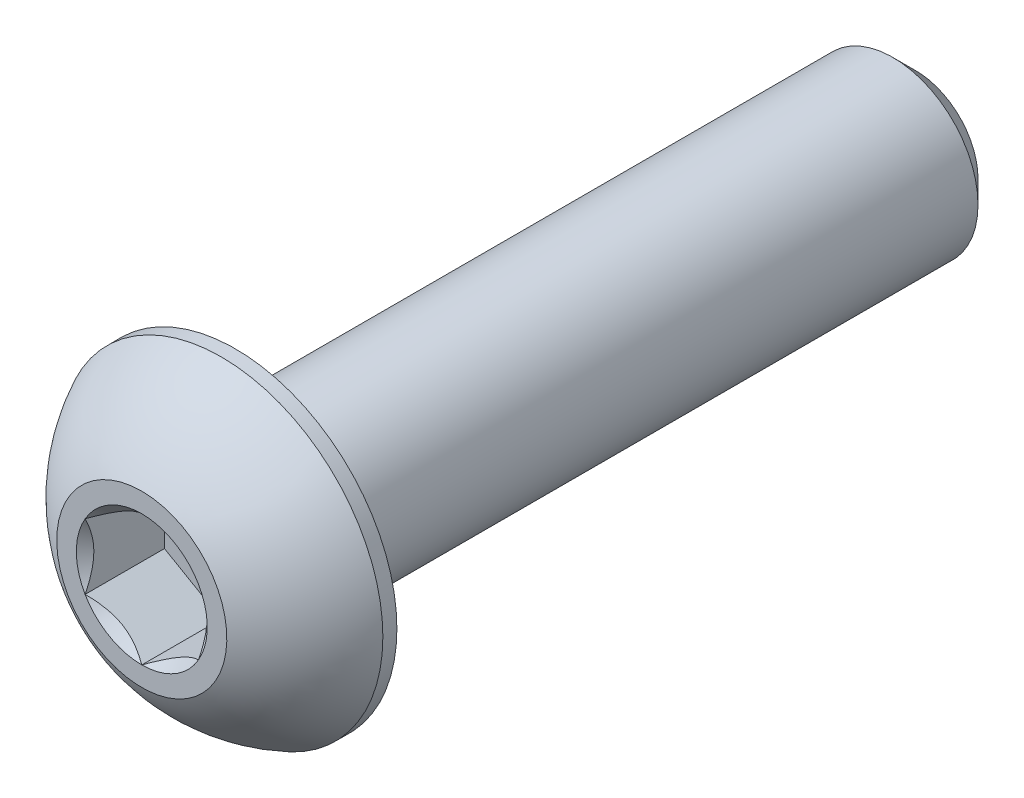
SolidWorks part; units mm, degrees
material "Alloy Steel"
ref_plane "Front Plane" through (0, 0, 0) normal (0, 0, 1) x (1, 0, 0)
ref_plane "Top Plane" through (0, 0, 0) normal (0, 1, 0) x (1, 0, 0)
ref_plane "Right Plane" through (0, 0, 0) normal (1, 0, 0) x (0, 0, -1)
sketch "Sketch1" plane through (0, 0, 0) normal (1, 0, 0) x (0, 0, -1)
  line L0 (-6.825, 0) -> (6.825, 0) construction
  line L1 (-5.175, 2.85) -> (-5.175, -2.85) construction
  line L2 (6.825, 1.5) -> (6.825, -1.5) construction
  line L3 (6.7937, 1.5541) -> (7.0437, 1.1211) construction
  line L4 (7.0437, 1.1211) -> (7.2938, 1.5541) construction
  line L5 (7.2938, 1.5541) -> (6.7937, 1.5541) construction
  line L6 (6.825, 1.5) -> (7.2625, 1.5) construction
  line L7 (7.0437, 1.5541) -> (7.0437, 1.5) construction
  line L8 (7.0437, 1.5) -> (7.0437, 1.1752) construction
  line L9 (7.0437, 1.1752) -> (7.0437, 1.1211) construction
  line L10 (7.0125, 1.1752) -> (7.075, 1.1752)
  line L11 (6.8094, 1.5271) -> (7.2781, 1.5271)
  line L12 (7.075, 1.1752) -> (7.2781, 1.5271)
  line L13 (7.0125, 1.1752) -> (6.8094, 1.5271)
  line L14 (-6.825, 1) -> (-6.825, -1) construction
  line L15 (6.825, 1.5) -> (-5.175, 1.5) construction
  point P3 (-5.175, 0)
  point P6 (-5.425, 0)
  point P21 (7.0437, 1.5271)
  point P24 (-5.4225, 2.85)
  point P25 (5.575, -1.5)
  point P26 (-6.825, 1.5)
  dimension "Head Height" = 1.65
  dimension "Length" = 12
  dimension "Head Dia" = 5.7
  dimension "Thread Dia" = 3
  dimension "Pitch" = 0.5
  dimension "D2" = 0.0625
  dimension "Drive Size" = 2
  dimension "D1" = 1.4
  dimension "D3" = 0.2475
  dimension "D4" = 1.25
sketch "Sketch2" plane through (0, 0, 0) normal (1, 0, 0) x (0, 0, -1)
  line L0 (-6.825, 0) -> (6.825, 0)
  line L1 (6.825, 0) -> (6.825, 1.1)
  line L2 (6.825, 1.5) -> (6.825, -1.5) construction
  line L3 (6.825, 1.1) -> (6.425, 1.5)
  line L4 (6.425, 1.5) -> (-5.175, 1.5)
  line L5 (-5.175, 2.85) -> (-5.175, -2.85) construction
  line L6 (-5.175, 1.5) -> (-5.175, 2.85)
  line L7 (-5.175, 2.85) -> (-5.4225, 2.85)
  line L8 (6.825, 1.5) -> (7.2625, 1.5) construction
  line L9 (-6.825, 0) -> (-6.825, 1.5)
  arc A0 (-6.825, 1.5) -> (-5.4225, 2.85) centre (-4.0302, 0) cw
  dimension "D1" = 0.4
  dimension "D2" = 45
revolve "Revolve1" add sketch "Sketch2" angle 360 about L0
sketch "Sketch3" plane through (0, 0, 6.825) normal (0, 0, 1) x (1, 0, 0)
  line L1 (0, 1.1547) -> (-1, 0.5774)
  line L2 (-1, 0.5774) -> (-1, -0.5774)
  line L3 (-1, -0.5774) -> (0, -1.1547)
  line L4 (0, -1.1547) -> (1, -0.5774)
  line L5 (1, -0.5774) -> (1, 0.5774)
  line L6 (1, 0.5774) -> (0, 1.1547)
  circle A0 centre (0, 0) radius 1 construction
  dimension "D1" = 2
extrude "Cut-Extrude1" cut sketch "Sketch3" against normal up to vertex (1.4 mm away) up to point (0, 0, 5.425)
sketch "Sketch4" plane through (0, 0, 6.825) normal (0, 0, 1) x (1, 0, 0)
  circle A0 centre (0, 0) radius 1.1547
extrude "Cut-Extrude2" cut sketch "Sketch4" against normal blind 10 draft 45
split "Split1" [suppressed] bodies to split 106
sketch "Sketch5" [suppressed] plane through (0, 0, -6.825) normal (0, 0, -1) x (-1, 0, 0)
  circle A0 centre (0, 0) radius 1.5 construction
  circle A1 centre (0, 0) radius 1.5
curve "Helix/Spiral1" [suppressed] pitch 0.5 height 12.5 turns 25
sketch "Sketch6" [suppressed] plane through (0, 0, 0) normal (1, 0, 0) x (0, 0, -1)
  line L0 (7.0125, 1.1752) -> (7.075, 1.1752) construction
  line L1 (7.0125, 1.1752) -> (6.8094, 1.5271) construction
  line L2 (6.8094, 1.5271) -> (7.2781, 1.5271) construction
  line L3 (7.075, 1.1752) -> (7.2781, 1.5271) construction
  line L4 (7.0125, 1.1752) -> (7.075, 1.1752)
  line L5 (7.0125, 1.1752) -> (6.8094, 1.5271)
  line L6 (6.8094, 1.5271) -> (7.2781, 1.5271)
  line L7 (7.075, 1.1752) -> (7.2781, 1.5271)
sweep "Cut-Sweep1" [suppressed] cut profiles "Sketch6" path "Helix/Spiral1"
sketch "Sketch7" [suppressed] plane through (0, 0, 5.175) normal (0, 0, -1) x (-1, 0, 0)
  circle A1 centre (0, 0) radius 1.5
  circle A2 centre (0, 0) radius 1.5
  dimension "D1" = 0
extrude "Boss-Extrude1" [suppressed] add sketch "Sketch7" along normal blind 10 draft 30
equation "\"D2@Sketch1\" = \"Pitch@Sketch1\" / 8"
equation "\"D1@Sketch1\"=\"Drive Size@Sketch1\"*.7"
equation "\"D3@Sketch1\"=\"Head Height@Sketch1\"*.15"
equation "\"D1@Sketch2\"=\"Pitch@Sketch1\"*.8"
equation "\"D1@Sketch3\"=\"Drive Size@Sketch1\""
equation "\"D4@Helix/Spiral1\"=\"Pitch@Sketch1\""
equation "\"D3@Helix/Spiral1\"=\"Length@Sketch1\"+\"Pitch@Sketch1\""
equation "\"D4@Sketch1\"=\"Pitch@Sketch1\"*2.5"
